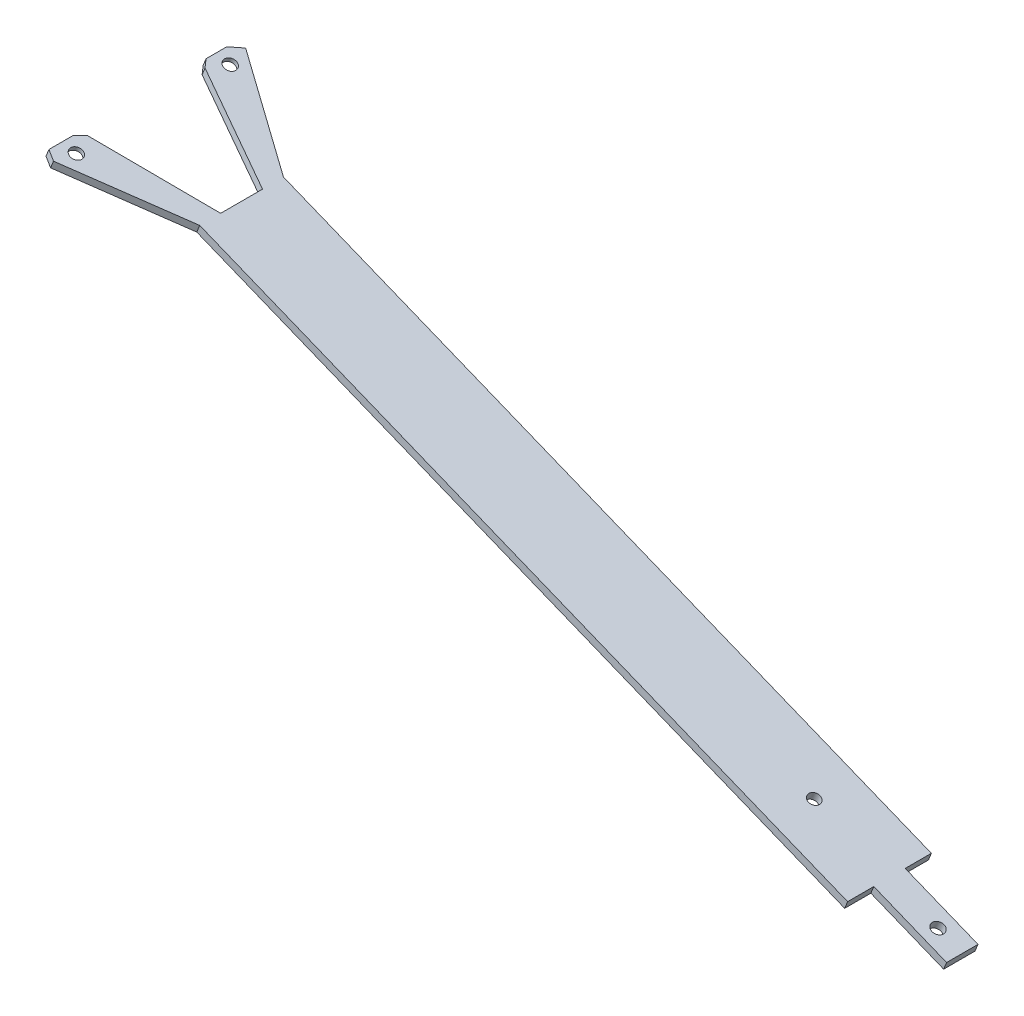
SolidWorks part; units mm, degrees
ref_plane "Front Plane" through (0, 0, 0) normal (0, 0, 1) x (1, 0, 0)
ref_plane "Top Plane" through (0, 0, 0) normal (0, 1, 0) x (1, 0, 0)
ref_plane "Right Plane" through (0, 0, 0) normal (1, 0, 0) x (0, 0, -1)
sketch "Sketch2" plane through (21.2561, 52.6275, 0) normal (-0.3745, -0.9272, 0) x (0.9272, -0.3745, 0)
  line L0 (100.747, -97) -> (100.747, -102)
  line L1 (100.747, -97) -> (-32.753, -97)
  line L2 (115.747, -102) -> (115.747, -108)
  line L3 (100.747, -113) -> (-32.753, -113)
  line L4 (-32.753, -97) -> (-32.753, -113)
  line L5 (100.747, -102) -> (115.747, -102)
  line L6 (115.747, -108) -> (100.747, -108)
  line L7 (100.747, -108) -> (100.747, -113)
  circle A2 centre (110.747, -105) radius 1.15
  circle A3 centre (85.247, -105) radius 1.1
  circle A4 centre (85.247, -105) radius 1.1 construction
  circle A5 centre (110.747, -105) radius 1.15 construction
  dimension "D8" = 2.2
  dimension "D9" = 2.3
  dimension "D1" = 16
  dimension "D2" = 148.5
  dimension "D3" = 5
  dimension "D4" = 5
  dimension "D5" = 15
  dimension "D6" = 5
  dimension "D7" = 8
extrude "Boss-Extrude1" add sketch "Sketch2" along normal blind 1.5
sketch "Sketch3" plane through (20.6943, 51.2367, 0) normal (-0.3745, -0.9272, 0) x (0.9272, -0.3745, 0)
  line L0 (-53.4718, -87.4061) -> (-53.4718, -92.053)
  line L1 (-53.4718, -92.053) -> (-52.3632, -93.798)
  line L2 (-51.9262, -123.553) -> (-53.4718, -121.3762)
  line L3 (-53.4718, -121.3762) -> (-53.4718, -117.4268)
  line L4 (-53.4718, -117.4268) -> (-52.3632, -116.201)
  line L5 (-52.4082, -115.039) -> (-52.3632, -116.201) construction
  line L6 (-52.3632, -116.201) -> (-51.3222, -117.243) construction
  line L7 (-51.9262, -123.553) -> (-32.753, -113)
  line L8 (-32.753, -97) -> (-51.648, -86.5853)
  line L17 (-32.753, -97) -> (-32.753, -101)
  line L19 (-52.3632, -116.201) -> (-32.753, -109)
  line L20 (-52.3632, -93.798) -> (-32.753, -101)
  line L23 (-51.648, -86.5853) -> (-53.4718, -87.4061)
  line L26 (-32.753, -109) -> (-32.753, -113)
  circle A0 centre (-50.9492, -119.7) radius 1.15 construction
  circle A2 centre (-50.9492, -119.7) radius 1.15
  circle A3 centre (-50.9492, -90.3) radius 1.15
  line M10 (-32.753, -97) -> (-32.753, -113)
  dimension "D1" = 4
  dimension "D2" = 4
  dimension "D4" = 2
extrude "Boss-Extrude2" add sketch "Sketch3" against normal up to surface (1.5 mm away) contours L23 L20 A3 M10 | L19 A2 region at (-19.9222, 67.6415, -93.962) region at (-19.8893, 67.6283, -115.9979)
sketch "Sketch4" plane through (20.6943, 51.2367, 0) normal (-0.3745, -0.9272, 0) x (0.9272, -0.3745, 0)
  circle A0 centre (-50.9492, -119.7) radius 2
  circle A1 centre (-50.9492, -90.3) radius 2
  dimension "D1" = 4
  dimension "D2" = 4
extrude "Cut-Extrude1" cut sketch "Sketch4" against normal blind 0.7
